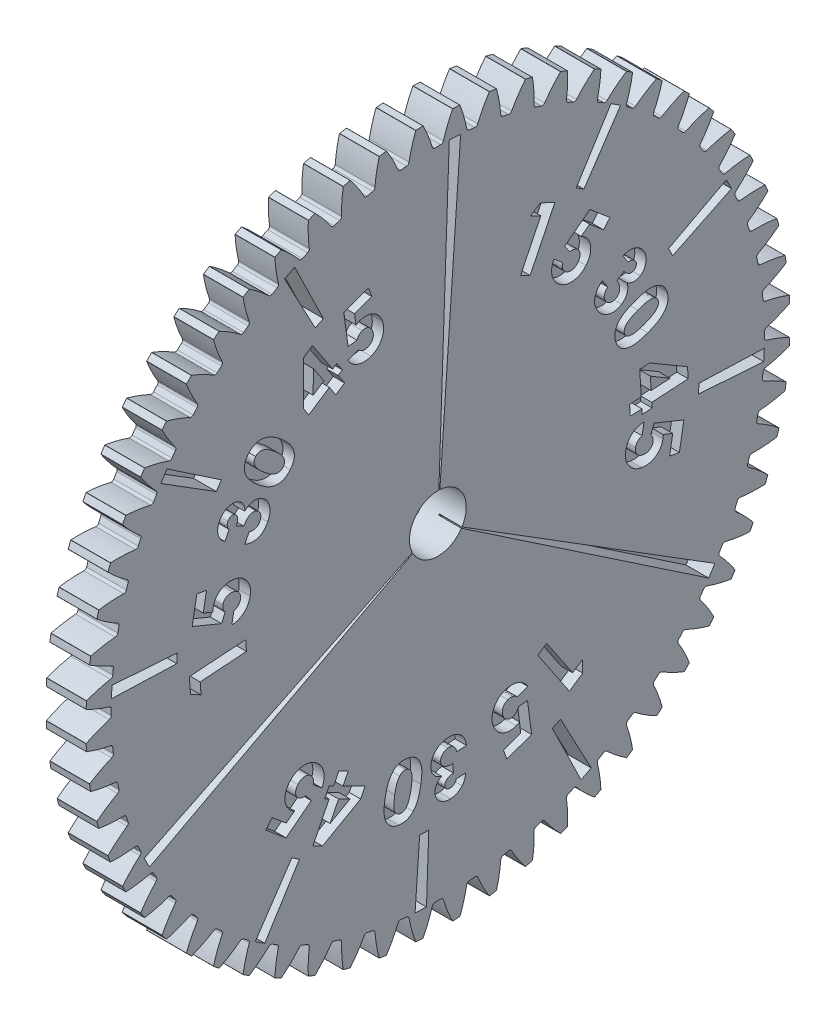
SolidWorks part; units mm, degrees
material "Cedar"
ref_plane "Plane1" through (0, 0, 0) normal (0, 0, 1) x (1, 0, 0)
ref_plane "Plane2" through (0, 0, 0) normal (0, 1, 0) x (1, 0, 0)
ref_plane "Plane3" through (0, 0, 0) normal (1, 0, 0) x (0, 0, -1)
sketch "HoldingSke" plane through (0, 0, 0) normal (0, 1, 0) x (1, 0, 0)
  line L0 (0, 0) -> (254, -439.9409)
  line L1 (-15, 0) -> (100, 0) construction
  line L2 (0, 0) -> (-2.1039, 2.3779)
  line L3 (0, 0) -> (-11.863, 4.5341)
  line L4 (0, 0) -> (4.318, 7.479)
  line L5 (0, 0) -> (-47.5972, -17.7524)
  line L6 (0, 0) -> (-3.6847, -2.4861)
  line L7 (-2.1039, 2.3779) -> (8.8308, 51.9871)
  line L8 (-76.2, 54.61) -> (-69.596, 54.61)
  line L9 (-71.009, 38.7566) -> (-53.1078, 45.2721)
  line L10 (-76.2, 71.12) -> (104.1128, 71.12)
  line L11 (0, 0) -> (-4.445, 0)
  line L12 (-76.2, 101.6) -> (-76.1492, 101.6)
  line L13 (24.9733, 27.94) -> (52.9518, 28.4284)
  line L14 (24.9733, 27.94) -> (25.0241, 27.9398)
  line L15 (24.9733, 27.94) -> (100.4021, 29.52)
  circle A0 centre (0, 0) radius 3.175
  circle A1 centre (0, 0) radius 36.5252
  circle A2 centre (0, 0) radius 38.1
  circle A3 centre (0, 0) radius 3.175
  dimension "MHD" = 73.0504
  dimension "Hub_dia" = 76.2
  dimension "Bore" = 6.35
  dimension "MBD" = 6.35
  dimension "Num_teeth" = 60
  dimension "Pitch_radius" = 180.3128
  dimension "Pitch" = 508
  dimension "Width" = 4.445
  dimension "Overall_len" = 50.8
  dimension "Show_teeth" = 60
  dimension "Thickness" = 4.445
  dimension "OAL" = 50.8001
  dimension "T_dim" = 6.604
  dimension "Ap" = 20
  dimension "H" = 19.05
  dimension "Backlash" = 0.0508
  dimension "Addendum_fac" = 1
  dimension "Dedendum_fac" = 1.2
  dimension "Clearance_fac" = 0.2
  dimension "Dedendum_add" = 0.0508
sketch "BasProSke" plane through (0, 0, 0) normal (0, 1, 0) x (1, 0, 0)
  line L0 (-10, 0) -> (60, 0) construction
  line L1 (0, 0) -> (0, 39.37)
  line L2 (0, 0) -> (4.445, 0)
  line L3 (4.445, 0) -> (4.445, 39.37)
  line L4 (4.445, 39.37) -> (0, 39.37)
  dimension "Diameter" = 78.74
  dimension "Thickness" = 4.445
revolve "Base-Revolve" add sketch "BasProSke" angle 360 about L0
sketch "TooCutSke" plane through (0, 0, 0) normal (1, 0, 0) x (0, 0, -1)
  line L1 (0, 0) -> (0, 107) construction
  line L2 (0, 0) -> (-1.0862, 38.0845) construction
  line L3 (0, 0) -> (-3.9869, 76.0739) construction
  line L4 (-1.0862, 38.0845) -> (-1.9934, 38.037) construction
  arc A0 (0.5545, 36.521) -> (-0.5545, 36.521) centre (0, 0) ccw
  arc A1 (1.6683, 39.3601) -> (-1.6683, 39.3601) centre (0, 0) ccw
  circle A2 centre (0, 0) radius 38.1 construction
  circle A3 centre (0, 0) radius 35.8023 construction
  arc A4 (-0.5545, 36.521) -> (-1.6683, 39.3601) centre (-15.2274, 32.4026) ccw
  arc A5 (1.6683, 39.3601) -> (0.5545, 36.521) centre (15.2274, 32.4026) ccw
  dimension "Root_dia" = 73.0504
  dimension "Overcut_dia" = 78.7908
  dimension "Pitch_dia" = 76.2
  dimension "Base_dia" = 71.6046
  dimension "Flank_rad" = 15.24
  dimension "Half_ang" = 3
  dimension "Half_CT" = 0.9084
extrude "ToothCut" cut sketch "TooCutSke" along normal through all
fillet "Breaks" radius 0.0254 2 edges at (2.2225, 39.3352, -1.6555) (2.2225, 39.3352, 1.6555)
fillet "RootFillets" radius 0.3048 2 edges at (2.2225, 36.521, -0.5545) (2.2225, 36.521, 0.5545)
pattern_circular "TeethCuts" count 60 every 6 about axis through (-10, 0, 0) along (1, 0, 0) of "ToothCut", "RootFillets", "Breaks"
sketch "HubNeaOneSke" plane through (0, 0, 0) normal (-1, 0, 0) x (0, 0, 1)
  circle A0 centre (0, 0) radius 36.5252
  dimension "Diameter" = 73.0504
extrude "HubNearOne" [suppressed] add sketch "HubNeaOneSke" along normal blind 46.3551
sketch "HubNeaBotSke" plane through (0, 0, 0) normal (-1, 0, 0) x (0, 0, 1)
  circle A0 centre (0, 0) radius 36.5252
  dimension "Diameter" = 73.0504
extrude "HubNearBoth" [suppressed] add sketch "HubNeaBotSke" along normal blind 23.1775
ref_plane "FarPln" through (4.445, 0, 0) normal (1, 0, 0) x (0, 0, -1)
sketch "HubFarSke" plane through (4.445, 0, 0) normal (1, 0, 0) x (0, 0, -1)
  circle A0 centre (0, 0) radius 36.5252
  dimension "Diameter" = 73.0504
extrude "HubFar" [suppressed] add sketch "HubFarSke" along normal blind 23.1775
sketch "BorSke" plane through (0, 0, 0) normal (1, 0, 0) x (0, 0, -1)
  circle A0 centre (0, 0) radius 3.175
  dimension "Diameter" = 6.35
extrude "Bore" cut sketch "BorSke" along normal mid plane 101.6001
sketch "KeySke" plane through (0, 0, 0) normal (1, 0, 0) x (0, 0, -1)
  line L0 (-0.127, 0) -> (-0.127, 3.429)
  line L1 (-0.127, 3.429) -> (0.127, 3.429)
  line L2 (0.127, 3.429) -> (0.127, 0)
  line L3 (0, 0) -> (0, 34) construction
  line L4 (-0.127, 0) -> (0.127, 0)
  dimension "Offset" = 3.429
  dimension "Width" = 0.254
extrude "Keyway" [suppressed] cut sketch "KeySke" along normal mid plane 101.6001
pattern_circular "Keyway2" [suppressed] count 2 every 90 about axis through (-10, 0, 0) along (1, 0, 0)
sketch "Sketch2" plane through (4.445, 0, 0) normal (1, 0, 0) x (0, 0, -1)
  line L0 (0, 0) -> (2.0605, 39.316) construction
  line L1 (0, 0) -> (35.727, 7.594) construction
  line L2 (0, 0) -> (11.2869, 34.7375) construction
  line L3 (0, 0) -> (27.1435, 24.4401) construction
  line L4 (0, 0) -> (34.7375, -11.2869) construction
  arc A0 (6.6717, 20.5333) -> (16.0445, 14.4465) centre (0, 0) cw construction
  circle A1 centre (0, 0) radius 36.5252 construction
  arc A2 (-3.4962, 36.3575) -> (-4.1393, 36.2899) centre (0, 0) ccw construction
  arc A3 (16.0445, 14.4465) -> (21.1182, 4.4888) centre (0, 0) cw construction
  arc A4 (21.1182, 4.4888) -> (20.5333, -6.6717) centre (0, 0) cw construction
  arc A8 (2.4489, 39.2938) -> (1.6718, 39.3345) centre (0, 0) ccw construction
  text T0 "15" font "Century Gothic" height in points 24
  text T1 "30" font "Century Gothic" height in points 22
  text T2 "45" font "Century Gothic" height in points 24
  point P18 (2.0605, 39.316)
  dimension "D1" = 15
  dimension "D2" = 30
  dimension "D3" = 21.59
  dimension "D4" = 30
  dimension "D5" = 30
extrude "Text" cut sketch "Sketch2" against normal blind 1.27
pattern_circular "CirPattern1" count 3 every 120 about axis through (4.445, 0, 0) along (-1, 0, 0) of "Text"
sketch "Sketch3" plane through (4.445, 0, 0) normal (1, 0, 0) x (0, 0, -1)
  line L0 (0, 0) -> (1.9116, 36.4751)
  line L1 (0, 0) -> (1.2747, 36.5029)
  line L2 (0, 0) -> (2.5479, 36.4362)
  line L3 (0, 0) -> (19.893, 30.6326)
  line L4 (0, 0) -> (19.3554, 30.9751)
  line L5 (0, 0) -> (20.4246, 30.2808)
  line L6 (0, 0) -> (32.2498, 17.1475)
  line L7 (0, 0) -> (32.8286, 16.0116)
  line L8 (0, 0) -> (36.5029, -1.2747)
  line L9 (0, 0) -> (36.4362, -2.5479)
  line L10 (0, 0) -> (0, 36.5252)
  arc A0 (0.3233, 36.5238) -> (-0.3233, 36.5238) centre (0, 0) ccw construction
  circle A1 centre (0, 0) radius 36.5252
  circle A2 centre (0, 0) radius 29.21
  point P20 (0, 0)
  point P21 (0, 0)
  dimension "D4" = 58.42
  dimension "D1" = 1
  dimension "D2" = 1
  dimension "D3" = 30
  dimension "D5" = 1
  dimension "D6" = 1
  dimension "D8" = 30
  dimension "D9" = 3
  dimension "D7" = 3
extrude "Cut-Extrude2" cut sketch "Sketch3" against normal blind 2.54 contours A2 L0 A1 L1 | A2 L2 A1 L0 | L2 A2 L0 | L0 A2 L1 | A2 L5 A1 L3 | A2 L3 A1 L4 | A2 L9 A1 L8 | A2 L7 A1 L6
pattern_circular "CirPattern2" count 3 every 120 about axis through (0, 0, 0) along (1, 0, 0) of "Cut-Extrude2"
sketch "Sketch4" plane through (4.445, 0, 0) normal (1, 0, 0) x (0, 0, -1)
  line L0 (0, 0) -> (1.994, 38.0478)
  circle A0 centre (0, 0) radius 38.1
  arc A1 (2.5479, 36.4362) -> (1.2747, 36.5029) centre (0, 0) ccw construction
  point P3 (1.9116, 36.4751)
  dimension "D1" = 76.2
equation "' \"Pitch@HoldingSke\" = 4"
equation "' \"Num_teeth@HoldingSke\" = 12"
equation "' \"Ap@HoldingSke\" =  20"
equation "' \"Width@HoldingSke\" = 0.5"
equation "' \"Hub_dia@HoldingSke\"= 1"
equation "' \"Overall_len@HoldingSke\" = 1.0"
equation "' \"Bore@HoldingSke\" = 0.75"
equation "' \"T_dim@HoldingSke\" = 0.85"
equation "' \"Width@KeySke\" = 0.25"
equation "' \"Show_teeth@HoldingSke\" = 13"
equation "' \"Backlash@HoldingSke\" = 0.009"
equation "' \"Addendum_fac@HoldingSke\" = 1.0"
equation "' \"Dedendum_fac@HoldingSke\" = 1.25"
equation "' \"Dedendum_add@HoldingSke\" = 0.00005"
equation "' \"Clearance_fac@HoldingSke\" = 0.25"
equation "' \"Pitch@HoldingSke\" = 0.5"
equation "' \"Num_teeth@HoldingSke\" = 23"
equation "' \"Show_teeth@HoldingSke\" = 23"
equation "' \"Backlash@HoldingSke\" = 0.0375"
equation "\"Overcut_dia@TooCutSke\" = (\"Num_teeth@HoldingSke\" + 2 * \"Addendum_fac@HoldingSke\") / \"Pitch@HoldingSke\" + 0.002"
equation "\"Pitch_dia@TooCutSke\" = \"Num_teeth@HoldingSke\" / \"Pitch@HoldingSke\""
equation "\"Base_dia@TooCutSke\" = \"Num_teeth@HoldingSke\" / \"Pitch@HoldingSke\" * cos((\"Ap@HoldingSke\"  * 3.14159265 / 180))"
equation "\"Root_dia@TooCutSke\" = (\"Num_teeth@HoldingSke\" + 2) / \"Pitch@HoldingSke\" - 2 * (\"Addendum_fac@HoldingSke\" + \"Dedendum_fac@HoldingSke\") / \"Pitch@HoldingSke\" - \"Dedendum_add@HoldingSke\" * 2"
equation "\"Half_ang@TooCutSke\" = 180 / \"Num_teeth@HoldingSke\""
equation "\"Half_CT@TooCutSke\" = \"Num_teeth@HoldingSke\" / \"Pitch@HoldingSke\" * sin((3.14159265 / 2 / \"Num_teeth@HoldingSke\")) / 2 - 7 * \"Backlash@HoldingSke\" / 4"
equation "\"Flank_rad@TooCutSke\" = \"Num_teeth@HoldingSke\" / \"Pitch@HoldingSke\" / 5"
equation "\"Radius@RootFillets\" = \"Clearance_fac@HoldingSke\" / \"Pitch@HoldingSke\" + \"Dedendum_add@HoldingSke\""
equation "\"Break_rad@Breaks\" = 0.02 / \"Pitch@HoldingSke\""
equation "\"Thickness@HoldingSke\" = \"Width@HoldingSke\""
equation "\"OAL@HoldingSke\" = \"Thickness@HoldingSke\""
equation "\"MHD@HoldingSke\" = (\"Num_teeth@HoldingSke\" + 2) / \"Pitch@HoldingSke\" - 2 * (\"Addendum_fac@HoldingSke\" + \"Dedendum_fac@HoldingSke\")  / \"Pitch@HoldingSke\" - \"Dedendum_add@HoldingSke\" * 2"
equation "\"MBD@HoldingSke\" = (\"Num_teeth@HoldingSke\" + 2) / \"Pitch@HoldingSke\" - 2 * (\"Addendum_fac@HoldingSke\" + \"Dedendum_fac@HoldingSke\")  / \"Pitch@HoldingSke\" - \"Dedendum_add@HoldingSke\" * 2 - 0.002"
equation "\"MHD@HoldingSke\" = ((sgn( \"MHD@HoldingSke\" - \"Hub_dia@HoldingSke\" )-1)*( \"MHD@HoldingSke\" - \"Hub_dia@HoldingSke\" ))/-2+ \"Hub_dia@HoldingSke\""
equation "\"MBD@HoldingSke\" = ((sgn( \"MBD@HoldingSke\" - \"Bore@HoldingSke\" )-1)*( \"MBD@HoldingSke\" - \"Bore@HoldingSke\" ))/-2+ \"Bore@HoldingSke\""
equation "\"OAL@HoldingSke\" = ((sgn( \"OAL@HoldingSke\" - \"Overall_len@HoldingSke\" )+1)*( \"OAL@HoldingSke\" - \"Overall_len@HoldingSke\" ))/2 + \"Overall_len@HoldingSke\" + 0.000002"
equation "\"Num_teeth@TeethCuts\" = int( \"Show_teeth@HoldingSke\" ) + 1"
equation "\"Num_teeth@TeethCuts\" = ((sgn( \"Num_teeth@TeethCuts\" - \"Num_teeth@HoldingSke\" )-1)*( \"Num_teeth@TeethCuts\" - \"Num_teeth@HoldingSke\" ))/-2+ \"Num_teeth@HoldingSke\""
equation "\"Num_teeth@TeethCuts\" = ((sgn( \"Num_teeth@TeethCuts\" - 2.0)+1)*( \"Num_teeth@TeethCuts\" - 2.0))/2 +2.0"
equation "\"Angle@TeethCuts\" = 360.0 / \"Num_teeth@HoldingSke\""
equation "\"Diameter@BasProSke\" = (\"Num_teeth@HoldingSke\" + 2 * \"Addendum_fac@HoldingSke\") / \"Pitch@HoldingSke\""
equation "\"Thickness@BasProSke\"  = \"Thickness@HoldingSke\""
equation "' \"Fillet_rad@BasProSke\" =  \"Thickness@HoldingSke\" * 0.05"
equation "\"MHD@HoldingSke\" = ((sgn( \"MHD@HoldingSke\" - \"Root_dia@TooCutSke\" )-1)*( \"MHD@HoldingSke\" - \"Root_dia@TooCutSke\" ))/-2+ \"Root_dia@TooCutSke\""
equation "\"Diameter@HubNeaOneSke\" = \"MHD@HoldingSke\""
equation "\"Length@HubNearOne\" = \"OAL@HoldingSke\" - \"Thickness@BasProSke\""
equation "\"Diameter@HubNeaBotSke\" = \"MHD@HoldingSke\""
equation "\"Length@HubNearBoth\" = ( \"OAL@HoldingSke\" - \"Thickness@BasProSke\" ) / 2.0"
equation "\"Thickness@FarPln\" = \"Thickness@BasProSke\""
equation "\"Diameter@HubFarSke\" = \"MHD@HoldingSke\""
equation "\"Length@HubFar\" = ( \"OAL@HoldingSke\" - \"Thickness@BasProSke\" ) / 2.0"
equation "\"Diameter@BorSke\" = \"MBD@HoldingSke\""
equation "\"D1@Bore\" = \"OAL@HoldingSke\" * 2.0"
equation "\"D1@Keyway\" = \"OAL@HoldingSke\" * 2.0"
equation "\"Offset@KeySke\" = \"T_dim@HoldingSke\" - \"MBD@HoldingSke\" / 2.0"
